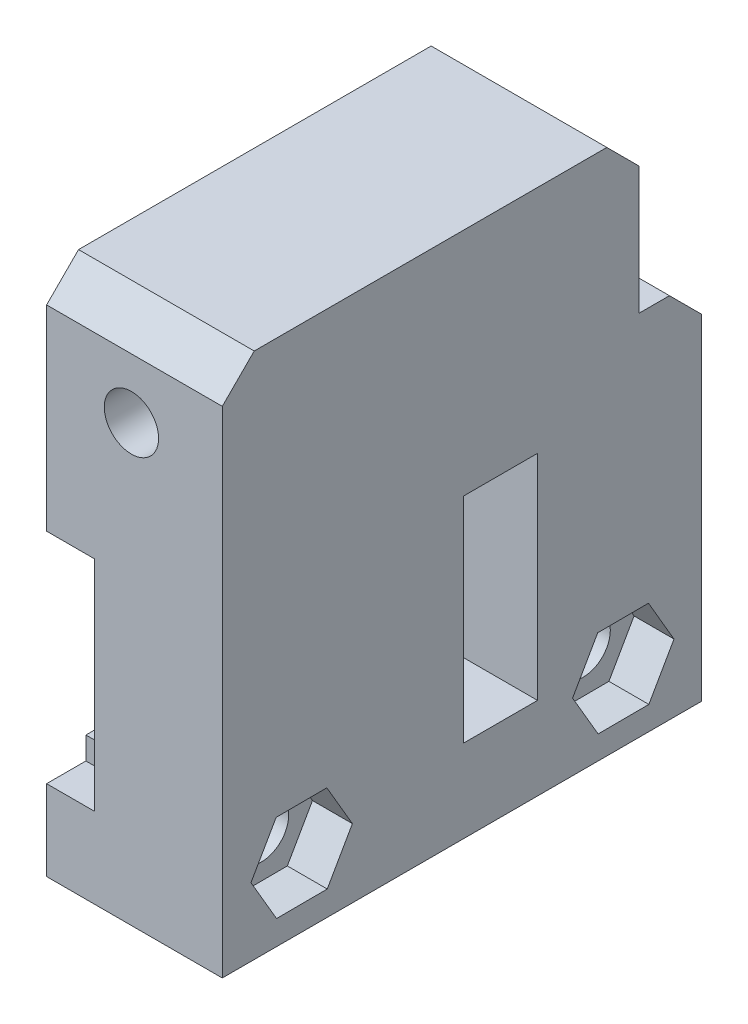
SolidWorks part; units mm, degrees
ref_plane "Front Plane" through (0, 0, 0) normal (0, 0, 1) x (1, 0, 0)
ref_plane "Top Plane" through (0, 0, 0) normal (0, 1, 0) x (1, 0, 0)
ref_plane "Right Plane" through (0, 0, 0) normal (1, 0, 0) x (0, 0, -1)
sketch "Sketch1" plane through (0, 0, 0) normal (1, 0, 0) x (0, 0, -1)
  line L1 (-15, 11.5) -> (15, 11.5)
  line L2 (-15, 11.5) -> (-15, -11.5)
  line L3 (-15, -11.5) -> (15, -11.5)
  line L4 (15, 11.5) -> (15, -11.5)
  line L5 (-15, 11.5) -> (15, -11.5) construction
  line L6 (-15, -11.5) -> (15, 11.5) construction
  point P0 (0, 0)
extrude "Boss-Extrude1" add sketch "Sketch1" along normal blind 11
sketch "Sketch2" plane through (0, 11.5, 0) normal (0, 1, 0) x (1, 0, 0)
  line L0 (11, 15) -> (11, -15) construction
  line L1 (0, -15) -> (11, -15)
  line L2 (0, -15) -> (0, 11.0781)
  line L3 (0, 11.0781) -> (11, 11.0781)
  line L4 (11, -15) -> (11, 11.0781)
  line L5 (0, -15) -> (11, 11.0781) construction
  line L6 (0, 11.0781) -> (11, -15) construction
  point P0 (5.5, -1.961)
extrude "Boss-Extrude2" add sketch "Sketch2" along normal blind 10
chamfer "Chamfer1" distance 2 angle 45 3 edges at (5.5, 11.5, -15) (5.5, 21.5, -11.0781) (5.5, 21.5, 15)
sketch "Sketch3" plane through (0, 0, 0) normal (-1, 0, 0) x (0, 0, 1)
  line L1 (-15.4578, 7.2288) -> (15.9867, 7.2288)
  line L2 (-15.4578, 7.2288) -> (-15.4578, -6.4617)
  line L3 (-15.4578, -6.4617) -> (15.9867, -6.4617)
  line L4 (15.9867, 7.2288) -> (15.9867, -6.4617)
  line L5 (-15.4578, 7.2288) -> (15.9867, -6.4617) construction
  line L6 (-15.4578, -6.4617) -> (15.9867, 7.2288) construction
  point P0 (0.2645, 0.3836)
  point P5 (-2.0921, 0)
extrude "Cut-Extrude2" cut sketch "Sketch3" against normal blind 3
sketch "Sketch4" plane through (3, 0.4351, 0) normal (-1, 0, 0) x (0, 0, 1)
  line L1 (-9.7361, 2.5) -> (5.2639, 2.5)
  line L2 (-9.7361, 2.5) -> (-9.7361, -2.5)
  line L3 (-9.7361, -2.5) -> (5.2639, -2.5)
  line L4 (5.2639, 2.5) -> (5.2639, -2.5)
  line L5 (-9.7361, 2.5) -> (5.2639, -2.5) construction
  line L6 (-9.7361, -2.5) -> (5.2639, 2.5) construction
  point P0 (-2.2361, 0)
  point P5 (-2.2361, 0)
extrude "Boss-Extrude3" add sketch "Sketch4" along normal blind 5
sketch "Sketch5" plane through (0, 0, 5.2639) normal (0, 0, 1) x (1, 0, 0)
  circle A0 centre (0.6342, 0.4547) radius 2.041
  point P2 (0, 0)
  point P4 (0, 0)
  point P5 (0, 0)
  point P6 (0.7454, 0.504)
  point P7 (0.3834, 0.4026)
  point P8 (0.5965, 0.4292)
  point P9 (0.6867, 0.5072)
  point P10 (0.6342, 0.4547)
extrude "Cut-Extrude3" cut sketch "Sketch5" against normal blind 15 contours A0
sketch "Sketch6" plane through (11, 0, 0) normal (1, 0, 0) x (0, 0, -1)
  line L1 (4.7403, 7.0824) -> (0.1188, 7.0824)
  line L2 (4.7403, 7.0824) -> (4.7403, -6.3163)
  line L3 (4.7403, -6.3163) -> (0.1188, -6.3163)
  line L4 (0.1188, 7.0824) -> (0.1188, -6.3163)
  line L5 (4.7403, 7.0824) -> (0.1188, -6.3163) construction
  line L6 (4.7403, -6.3163) -> (0.1188, 7.0824) construction
  point P0 (2.4296, 0.3831)
extrude "Cut-Extrude4" cut sketch "Sketch6" against normal blind 13 contours L4 L3 L2 L1
sketch "Sketch7" plane through (0, 0, 15) normal (0, 0, 1) x (1, 0, 0)
  circle A0 centre (5.3121, 15.7624) radius 1.7
  point P2 (4.8691, 15.3738)
  point P3 (4.7165, 15.7656)
  point P4 (0, 0)
  point P5 (5.3121, 15.7624)
extrude "Cut-Extrude5" cut sketch "Sketch7" against normal blind 27 contours A0
sketch "Sketch8" plane through (11, 0, 0) normal (1, 0, 0) x (0, 0, -1)
  line L1 (-8.4274, -9.9607) -> (-6.852, -7.2036)
  line L2 (-6.852, -7.2036) -> (-8.452, -4.4607)
  line L3 (-8.452, -4.4607) -> (-11.6274, -4.475)
  line L4 (-11.6274, -4.475) -> (-13.2028, -7.232)
  line L5 (-13.2028, -7.232) -> (-11.6028, -9.9749)
  line L6 (-11.6028, -9.9749) -> (-8.4274, -9.9607)
  circle A1 centre (-10.0274, -7.2178) radius 2.75 construction
  point P1 (63.5353, 31.3502)
  point P9 (63.5353, 31.3502)
  point P10 (-2.7957, -7.3689)
  point P11 (-7.5909, -7.4321)
  point P12 (-10.0274, -7.232)
sketch "Sketch9" plane through (11, 0, 0) normal (1, 0, 0) x (0, 0, -1)
  line L1 (11.7097, -10.019) -> (13.2851, -7.262)
  line L2 (13.2851, -7.262) -> (11.6851, -4.5191)
  line L3 (11.6851, -4.5191) -> (8.5097, -4.5333)
  line L4 (8.5097, -4.5333) -> (6.9343, -7.2904)
  line L5 (6.9343, -7.2904) -> (8.5343, -10.0332)
  line L6 (8.5343, -10.0332) -> (11.7097, -10.019)
  circle A1 centre (10.1097, -7.2762) radius 2.75 construction
  point P1 (66.6598, 38.2156)
  point P9 (66.6598, 38.2156)
  point P10 (0.3289, -0.5034)
  point P11 (-4.4664, -0.5667)
  point P12 (10.7747, -7.8972)
  point P13 (10.8666, -7.206)
  point P14 (10.1097, -7.2904)
extrude "Cut-Extrude6" cut sketch "Sketch8" against normal blind 2.5
extrude "Cut-Extrude7" cut sketch "Sketch9" against normal blind 2.5
sketch "Sketch10" plane through (8.5, 0, 0) normal (1, 0, 0) x (0, 0, -1)
  circle A0 centre (10.0974, -7.2904) radius 1.7
  circle A1 centre (-10.0397, -7.232) radius 1.7
  point P4 (0, 0)
  point P5 (0, 0)
sketch "Sketch11" plane through (8.5, 0, 0) normal (1, 0, 0) x (0, 0, -1)
  line L1 (7.5967, -5.1102) -> (12.5981, -5.1102)
  line L2 (7.5967, -5.1102) -> (7.5967, -9.4706)
  line L3 (7.5967, -9.4706) -> (12.5981, -9.4706)
  line L4 (12.5981, -5.1102) -> (12.5981, -9.4706)
  line L5 (7.5967, -5.1102) -> (12.5981, -9.4706) construction
  line L6 (7.5967, -9.4706) -> (12.5981, -5.1102) construction
  point P0 (10.0974, -7.2904)
extrude "Boss-Extrude5" add sketch "Sketch11" against normal blind 8.5
sketch "Sketch12" plane through (8.5, 0, 0) normal (1, 0, 0) x (0, 0, -1)
  line L1 (-12.5404, -5.0518) -> (-7.539, -5.0518)
  line L2 (-12.5404, -5.0518) -> (-12.5404, -9.4122)
  line L3 (-12.5404, -9.4122) -> (-7.539, -9.4122)
  line L4 (-7.539, -5.0518) -> (-7.539, -9.4122)
  line L5 (-12.5404, -5.0518) -> (-7.539, -9.4122) construction
  line L6 (-12.5404, -9.4122) -> (-7.539, -5.0518) construction
  point P0 (-10.0397, -7.232)
  point P6 (-10.0397, -7.232)
extrude "Boss-Extrude6" add sketch "Sketch12" against normal blind 8.5
extrude "Cut-Extrude9" cut sketch "Sketch10" against normal blind 8.5
